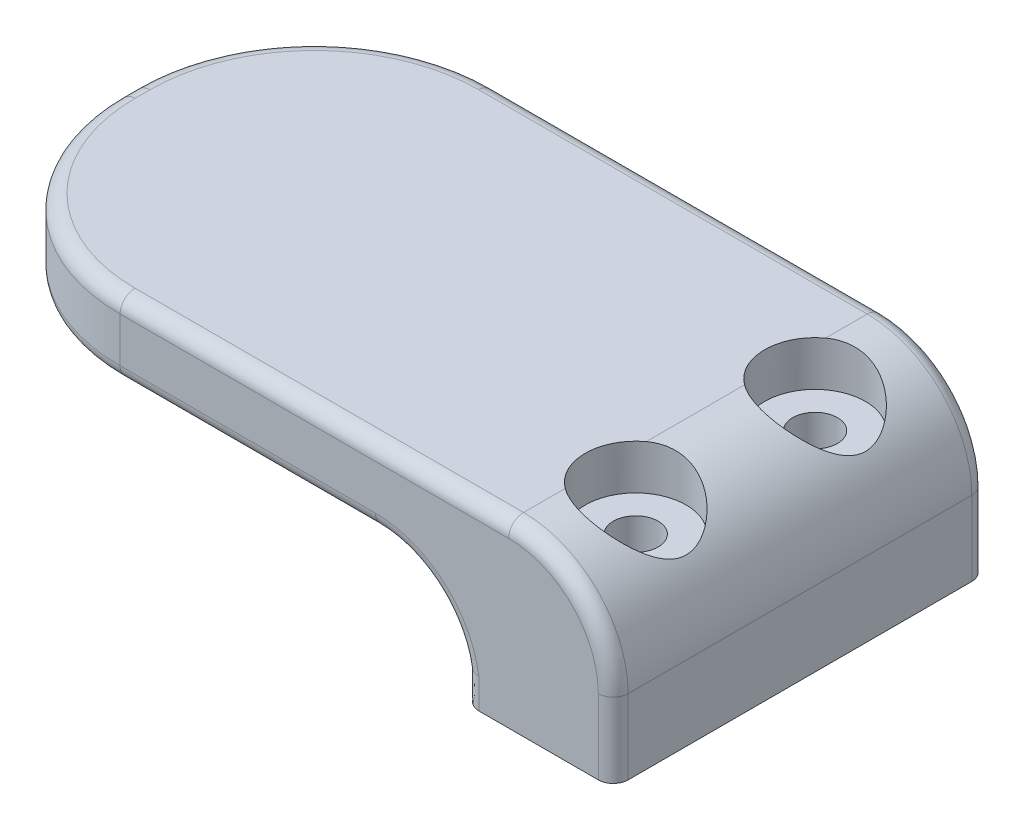
SolidWorks part; units mm, degrees
ref_plane "Alzado" through (0, 0, 0) normal (0, 0, 1) x (1, 0, 0)
ref_plane "Planta" through (0, 0, 0) normal (0, 1, 0) x (1, 0, 0)
ref_plane "Vista lateral" through (0, 0, 0) normal (1, 0, 0) x (0, 0, -1)
sketch "Croquis2" plane through (0, 0, 0) normal (0, 0, 1) x (1, 0, 0)
  line L1 (-22.5, -2.5) -> (12.5, -2.5)
  line L2 (-22.5, -2.5) -> (-22.5, 2.5)
  line L3 (-22.5, 2.5) -> (22.5, 2.5)
  line L4 (22.5, -2.5) -> (22.5, 2.5)
  line L5 (-22.5, -2.5) -> (22.5, 2.5) construction
  line L6 (-22.5, 2.5) -> (22.5, -2.5) construction
  line L8 (22.5, -2.5) -> (22.5, -7.5)
  line L9 (22.5, -7.5) -> (12.5, -7.5)
  line L10 (12.5, -2.5) -> (12.5, -7.5)
  point P0 (0, 0)
  dimension "D1" = 45
  dimension "D2" = 5
  dimension "D3" = 10
  dimension "D4" = 10
extrude "Saliente-Extruir1" add sketch "Croquis2" along normal mid plane 25
sketch "Croquis4" plane through (0, 2.5, 0) normal (0, 1, 0) x (1, 0, 0)
  line L0 (-22.5, -12.5) -> (-22.5, 12.5) construction
  circle A1 centre (-9.5, 0) radius 2.375
  dimension "D1" = 4.75
  dimension "D3" = 13
fillet "Redondeo1" radius 12 2 edges at (-22.5, 0, -12.5) (-22.5, 0, 12.5)
fillet "Redondeo2" radius 6 1 edges at (12.5, -2.5, 0)
fillet "Redondeo3" radius 1 14 edges at (6, 2.5, -12.5) (-18.9853, 2.5, -8.9853) (-22.5, 2.5, 0) (-18.9853, 2.5, 8.9853) (10.4569, -3.9174, -12.5) (-1.958, -2.5, -12.5) (-18.9853, -2.5, -8.9853) (-22.5, -2.5, 0) (-18.9853, -2.5, 8.9853) (10.4569, -3.9174, 12.5) (22.5, -2.5, -12.5) (22.5, -2.5, 12.5) (6, 2.5, 12.5) (-1.958, -2.5, 12.5)
sketch "Croquis6" plane through (0, -7.5, 0) normal (0, -1, 0) x (1, 0, 0)
  line L0 (17.5061, 15.0175) -> (17.5061, -15.0175) construction
  line L1 (13.5121, -12.5) -> (21.5, -12.5) construction
  circle A0 centre (17.5061, 0) radius 1.5
  circle A1 centre (17.5061, 6) radius 1.5
  circle A2 centre (17.5061, -6) radius 1.5
  dimension "D1" = 3
  dimension "D2" = 3
  dimension "D3" = 3
  dimension "D4" = 6
  dimension "D5" = 6
  dimension "D6" = 6.5
extrude "Saliente-Extruir3" add sketch "Croquis4" against normal blind 12 contours A1 region at (-9.5, 2.5, 0)
fillet "Redondeo4" radius 0.5 1 edges at (-9.5, -9.5, 2.375)
fillet "Redondeo5" radius 2 1 edges at (-11.875, -2.5, 0)
sketch "Croquis7" plane through (0, -7.5, 0) normal (0, -1, 0) x (1, 0, 0)
  line L4 (12.5, 11.5) -> (12.5, -11.5)
  line L5 (13.5121, -12.5) -> (21.5, -12.5)
  line L6 (22.5, -11.5) -> (22.5, 11.5)
  line L7 (21.5, 12.5) -> (13.5121, 12.5)
  line L8 (12.5, 11.5) -> (12.5, -11.5)
  line L9 (13.5121, -12.5) -> (21.5, -12.5)
  line L10 (22.5, -11.5) -> (22.5, 11.5)
  line L11 (21.5, 12.5) -> (13.5121, 12.5)
  arc A2 (21.5, -12.5) -> (22.5, -11.5) centre (21.5, -11.5) ccw
  arc A3 (22.5, 11.5) -> (21.5, 12.5) centre (21.5, 11.5) ccw
  arc A4 (21.5, -12.5) -> (22.5, -11.5) centre (21.5, -11.5) ccw
  arc A5 (22.5, 11.5) -> (21.5, 12.5) centre (21.5, 11.5) ccw
  spline S2 degree 3 poles (1378.1642, -2678.7025) (144.8606, 58.1746) (8.7047, -2.7144) (12.6292, -12.0059) (12.705, -12.1169) (12.8921, -12.3007) (13.0048, -12.3747) (21.1762, -15.7122) (76.724, 83.5237) (-2742.9791, 1166.2041) knots -18.643604 -18.643604 -18.643604 -18.643604 0.25 0.25 0.5 0.5 0.75 0.75 17.349418 17.349418 17.349418 17.349418 only from (12.5, -11.5) to (13.5121, -12.5)
  spline S3 degree 3 poles (-2688.7976, -1280.782) (85.254, -134.8533) (22.9362, 16.421) (13.0048, 12.3748) (12.8927, 12.3012) (6.4079, 5.9379) (88.0595, -88.5699) (1688.0966, 2497.2659) knots -19.829711 -19.829711 -19.829711 -19.829711 0.25 0.25 0.5 0.5 17.556102 17.556102 17.556102 17.556102 only from (13.5121, 12.5) to (12.5, 11.5)
  spline S4 degree 3 poles (12.5, -11.5) (12.5, -11.6328) (12.5267, -11.7632) (12.6292, -12.0059) (12.705, -12.1169) (12.8921, -12.3007) (13.0048, -12.3747) (13.2473, -12.4737) (13.3793, -12.5) (13.5121, -12.5) knots 0 0 0 0 0.25 0.25 0.5 0.5 0.75 0.75 1 1 1 1
  spline S5 degree 3 poles (13.5121, 12.5) (13.3793, 12.5) (13.249, 12.4743) (13.0048, 12.3748) (12.8927, 12.3012) (12.6117, 12.0254) (12.5, 11.7658) (12.5, 11.5) knots 0 0 0 0 0.25 0.25 0.5 0.5 1 1 1 1
  dimension "D1" = 0
extrude "Saliente-Extruir4" add sketch "Croquis7" along normal blind 2
extrude "Cortar-Extruir1" cut sketch "Croquis6" against normal through all both and the other way through all contours A1 L0 | L0 A1 | L0 A2 | A2 L0 region at (18.1427, -7.5, 6) region at (18.1427, -7.5, -6) region at (16.8694, -7.5, -6) region at (16.8694, -7.5, 6)
fillet "Redondeo6" radius 7 3 edges at (22.2071, 2.2071, -12.2071) (22.2071, 2.2071, 12.2071) (22.5, 2.5, 0)
sketch "Croquis8" plane through (0, 2.5, 0) normal (0, 1, 0) x (1, 0, 0)
  circle A0 centre (17.5061, -6) radius 3.375
  circle A1 centre (17.5061, 6) radius 3.375
  dimension "D1" = 6.75
extrude "Cortar-Extruir2" cut sketch "Croquis8" against normal blind 3
